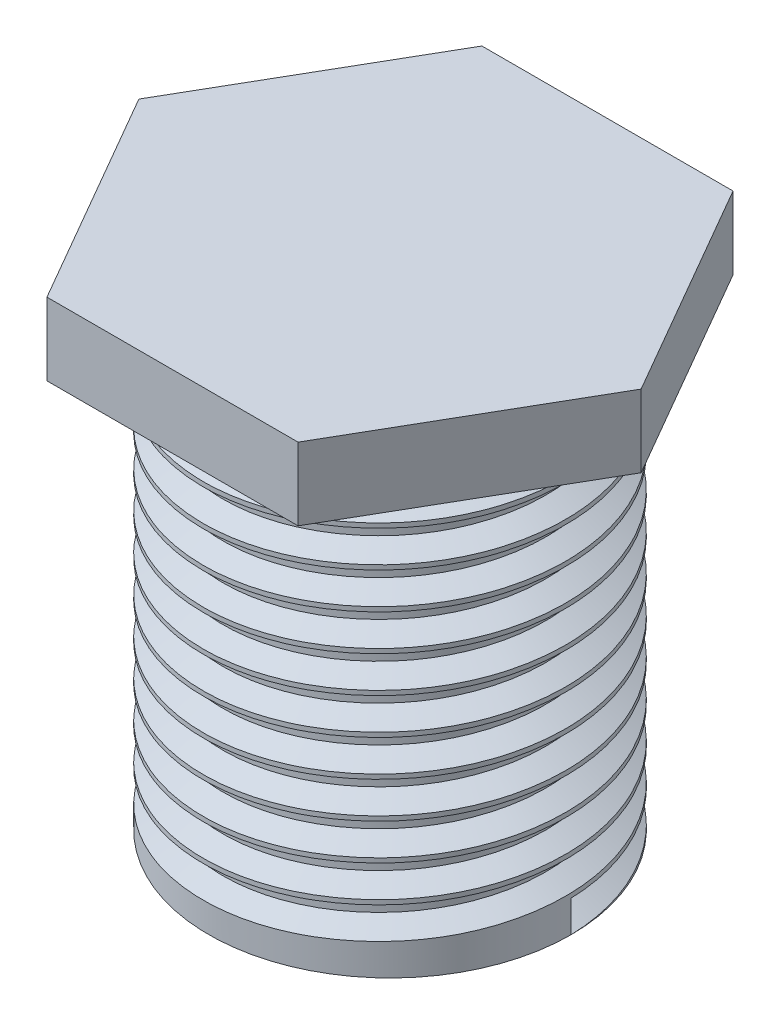
SolidWorks part; units mm, degrees
ref_plane "Front Plane" through (0, 0, 0) normal (0, 0, 1) x (1, 0, 0)
ref_plane "Top Plane" through (0, 0, 0) normal (0, 1, 0) x (1, 0, 0)
ref_plane "Right Plane" through (0, 0, 0) normal (1, 0, 0) x (0, 0, -1)
sketch "Sketch1" plane through (0, 0, 0) normal (0, 1, 0) x (1, 0, 0)
  circle A0 centre (0, 0) radius 5
extrude "Boss-Extrude1" add sketch "Sketch1" along normal blind 12
sketch "Sketch2" plane through (0, 12, 0) normal (0, 1, 0) x (1, 0, 0)
  line L1 (6.9282, 0) -> (3.4641, 6)
  line L2 (3.4641, 6) -> (-3.4641, 6)
  line L3 (-3.4641, 6) -> (-6.9282, 0)
  line L4 (-6.9282, 0) -> (-3.4641, -6)
  line L5 (-3.4641, -6) -> (3.4641, -6)
  line L6 (3.4641, -6) -> (6.9282, 0)
  circle A0 centre (0, 0) radius 6 construction
extrude "Boss-Extrude2" add sketch "Sketch2" along normal blind 2
thread "Thread1" pitch 1 method cut profile "Thread Profile1" start angle 0, offset 0, length 12, pitch 1, diameter 10
ref_plane "Plane1" through (5, 0, 0) normal (0, 0, 1) x (1, 0, 0)
sketch "Thread Profile1" plane through (5, 0, 0) normal (0, 0, 1) x (1, 0, 0)
  line L0 (0, 0) -> (0, 1) construction
  line L11 (0, 0) -> (0, 0.875)
  line L12 (0, 0.875) -> (-0.5413, 0.5625)
  line L13 (-0.5413, 0.5625) -> (-0.5413, 0.3125)
  line L15 (-0.5413, 0.3125) -> (0, 0)
  line L17 (-0.5413, 0.4375) -> (0, 0.4375) construction
  point P2 (0, 0)
  dimension "Pitch" = 1
  dimension "Profile_Angle" = 60
  dimension "Profile_Land" = 0.25
  dimension "Profile_Height" = 0.5413
